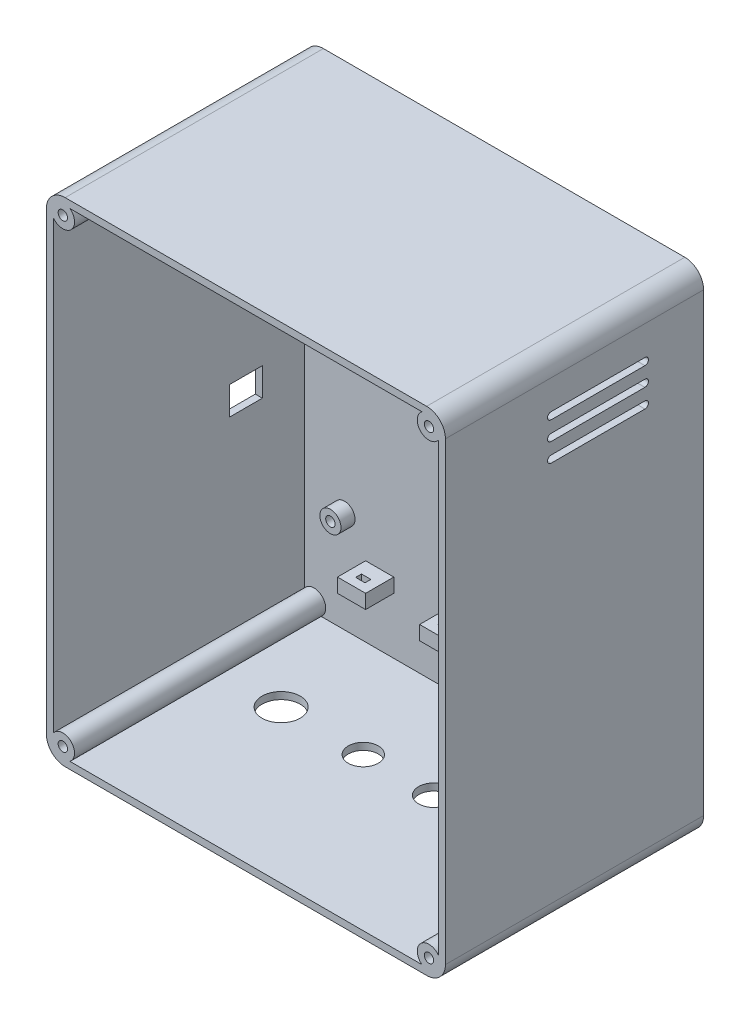
SolidWorks part; units mm, degrees
ref_plane "Front Plane" through (0, 0, 0) normal (0, 0, 1) x (1, 0, 0)
ref_plane "Top Plane" through (0, 0, 0) normal (0, 1, 0) x (1, 0, 0)
ref_plane "Right Plane" through (0, 0, 0) normal (1, 0, 0) x (0, 0, -1)
sketch "Sketch1" plane through (0, 0, 0) normal (0, 0, 1) x (1, 0, 0)
  line L0 (-77, 0) -> (77, 0)
  line L1 (85, 8) -> (85, 202)
  line L2 (77, 210) -> (-77, 210)
  line L3 (-85, 202) -> (-85, 8)
  arc A0 (-85, 8) -> (-77, 0) centre (-77, 8) ccw
  arc A1 (77, 0) -> (85, 8) centre (77, 8) ccw
  arc A2 (85, 202) -> (77, 210) centre (77, 202) ccw
  arc A3 (-77, 210) -> (-85, 202) centre (-77, 202) ccw
extrude "Block" add sketch "Sketch1" along normal blind 110
shell "Shell1" thickness 3 removed face at (0, 105, 110)
sketch "Sketch2" plane through (0, 0, 0) normal (0, 0, 1) x (1, 0, 0)
  circle A0 centre (-78, 7) radius 5
  circle A1 centre (78, 7) radius 5
  circle A2 centre (-78, 203) radius 5
  circle A3 centre (78, 203) radius 5
extrude "Corner columns" add sketch "Sketch2" along normal blind 110
ref_plane "P1_Front_110" through (0, 0, 110) normal (0, 0, 1) x (1, 0, 0)
sketch "Sketch3" plane through (0, 0, 110) normal (0, 0, 1) x (1, 0, 0)
  circle A0 centre (-78, 7) radius 2
  circle A1 centre (78, 7) radius 2
  circle A2 centre (-78, 203) radius 2
  circle A3 centre (78, 203) radius 2
extrude "Front panel insert holes" cut sketch "Sketch3" against normal blind 7
ref_plane "P2_Front_3" through (0, 0, 3) normal (0, 0, 1) x (1, 0, 0)
sketch "Sketch4" plane through (0, 0, 3) normal (0, 0, 1) x (1, 0, 0)
  circle A0 centre (-65, 46) radius 4.5
  circle A1 centre (65, 46) radius 4.5
  circle A2 centre (-65, 190) radius 4.5
  circle A3 centre (65, 190) radius 4.5
extrude "Plate bosses" add sketch "Sketch4" along normal blind 6
ref_plane "P3_Front_9" through (0, 0, 9) normal (0, 0, 1) x (1, 0, 0)
sketch "Sketch5" plane through (0, 0, 9) normal (0, 0, 1) x (1, 0, 0)
  circle A0 centre (-65, 46) radius 2
  circle A1 centre (65, 46) radius 2
  circle A2 centre (-65, 190) radius 2
  circle A3 centre (65, 190) radius 2
extrude "Plate insert holes" cut sketch "Sketch5" against normal blind 7
sketch "Sketch6" plane through (0, 0, 0) normal (0, 1, 0) x (1, 0, 0)
  circle A0 centre (-50, -45) radius 8.15
  circle A1 centre (-15, -45) radius 6.4
  circle A2 centre (15, -45) radius 6.4
  circle A3 centre (50, -45) radius 6.4
extrude "Cable gland holes" cut sketch "Sketch6" along normal blind 4
sketch "Sketch7" plane through (0, 0, 3) normal (0, 0, 1) x (1, 0, 0)
  line L1 (-56, 27) -> (-44, 27)
  line L2 (-56, 27) -> (-56, 33)
  line L3 (-56, 33) -> (-44, 33)
  line L4 (-44, 27) -> (-44, 33)
  line L5 (-56, 27) -> (-44, 33) construction
  line L6 (-56, 33) -> (-44, 27) construction
  line L7 (-21, 27) -> (-9, 27)
  line L8 (-21, 27) -> (-21, 33)
  line L9 (-21, 33) -> (-9, 33)
  line L10 (-9, 27) -> (-9, 33)
  line L11 (-21, 27) -> (-9, 33) construction
  line L12 (-21, 33) -> (-9, 27) construction
  line L13 (9, 27) -> (21, 27)
  line L14 (9, 27) -> (9, 33)
  line L15 (9, 33) -> (21, 33)
  line L16 (21, 27) -> (21, 33)
  line L17 (9, 27) -> (21, 33) construction
  line L18 (9, 33) -> (21, 27) construction
  line L19 (44, 27) -> (56, 27)
  line L20 (44, 27) -> (44, 33)
  line L21 (44, 33) -> (56, 33)
  line L22 (56, 27) -> (56, 33)
  line L23 (44, 27) -> (56, 33) construction
  line L24 (44, 33) -> (56, 27) construction
  point P0 (-50, 30)
  point P5 (-15, 30)
  point P10 (15, 30)
  point P15 (50, 30)
extrude "Cable tie bars" add sketch "Sketch7" along normal blind 12
ref_plane "P4_Top_26.99" through (0, 26.99, 0) normal (0, 1, 0) x (1, 0, 0)
sketch "Sketch8" plane through (0, 26.99, 0) normal (0, 1, 0) x (1, 0, 0)
  line L1 (-52, -11.25) -> (-48, -11.25)
  line L2 (-52, -11.25) -> (-52, -8.75)
  line L3 (-52, -8.75) -> (-48, -8.75)
  line L4 (-48, -11.25) -> (-48, -8.75)
  line L5 (-52, -11.25) -> (-48, -8.75) construction
  line L6 (-52, -8.75) -> (-48, -11.25) construction
  line L7 (-17, -11.25) -> (-13, -11.25)
  line L8 (-17, -11.25) -> (-17, -8.75)
  line L9 (-17, -8.75) -> (-13, -8.75)
  line L10 (-13, -11.25) -> (-13, -8.75)
  line L11 (-17, -11.25) -> (-13, -8.75) construction
  line L12 (-17, -8.75) -> (-13, -11.25) construction
  line L13 (13, -11.25) -> (17, -11.25)
  line L14 (13, -11.25) -> (13, -8.75)
  line L15 (13, -8.75) -> (17, -8.75)
  line L16 (17, -11.25) -> (17, -8.75)
  line L17 (13, -11.25) -> (17, -8.75) construction
  line L18 (13, -8.75) -> (17, -11.25) construction
  line L19 (48, -11.25) -> (52, -11.25)
  line L20 (48, -11.25) -> (48, -8.75)
  line L21 (48, -8.75) -> (52, -8.75)
  line L22 (52, -11.25) -> (52, -8.75)
  line L23 (48, -11.25) -> (52, -8.75) construction
  line L24 (48, -8.75) -> (52, -11.25) construction
  point P0 (-50, -10)
  point P5 (-15, -10)
  point P10 (15, -10)
  point P15 (50, -10)
extrude "Cable tie slots" cut sketch "Sketch8" along normal blind 6.02
ref_plane "P5_Right_-85" through (-85, 0, 0) normal (1, 0, 0) x (0, 0, -1)
sketch "Sketch9" plane through (-85, 0, 0) normal (1, 0, 0) x (0, 0, -1)
  line L1 (-35, 89) -> (-21, 89)
  line L2 (-35, 89) -> (-35, 101)
  line L3 (-35, 101) -> (-21, 101)
  line L4 (-21, 89) -> (-21, 101)
  line L5 (-35, 89) -> (-21, 101) construction
  line L6 (-35, 101) -> (-21, 89) construction
  point P0 (-28, 95)
extrude "USB access" cut sketch "Sketch9" along normal blind 4
ref_plane "P6_Right_-85" through (-85, 0, 0) normal (1, 0, 0) x (0, 0, -1)
sketch "Sketch10" plane through (-85, 0, 0) normal (1, 0, 0) x (0, 0, -1)
  line L0 (-25, 172) -> (-65, 172) construction
  line L1 (-25, 170.5) -> (-65, 170.5)
  line L2 (-25, 173.5) -> (-65, 173.5)
  line L3 (-25, 180) -> (-65, 180) construction
  line L4 (-25, 178.5) -> (-65, 178.5)
  line L5 (-25, 181.5) -> (-65, 181.5)
  line L6 (-25, 188) -> (-65, 188) construction
  line L7 (-25, 186.5) -> (-65, 186.5)
  line L8 (-25, 189.5) -> (-65, 189.5)
  arc A0 (-25, 170.5) -> (-25, 173.5) centre (-25, 172) ccw
  arc A1 (-65, 173.5) -> (-65, 170.5) centre (-65, 172) ccw
  arc A2 (-25, 178.5) -> (-25, 181.5) centre (-25, 180) ccw
  arc A3 (-65, 181.5) -> (-65, 178.5) centre (-65, 180) ccw
  arc A4 (-25, 186.5) -> (-25, 189.5) centre (-25, 188) ccw
  arc A5 (-65, 189.5) -> (-65, 186.5) centre (-65, 188) ccw
  point P2 (-45, 172)
  point P7 (-45, 180)
  point P14 (-45, 188)
extrude "Vents left" cut sketch "Sketch10" along normal blind 4
ref_plane "P7_Right_85" through (85, 0, 0) normal (1, 0, 0) x (0, 0, -1)
sketch "Sketch11" plane through (85, 0, 0) normal (1, 0, 0) x (0, 0, -1)
  line L0 (-25, 172) -> (-65, 172) construction
  line L1 (-25, 170.5) -> (-65, 170.5)
  line L2 (-25, 173.5) -> (-65, 173.5)
  line L3 (-25, 180) -> (-65, 180) construction
  line L4 (-25, 178.5) -> (-65, 178.5)
  line L5 (-25, 181.5) -> (-65, 181.5)
  line L6 (-25, 188) -> (-65, 188) construction
  line L7 (-25, 186.5) -> (-65, 186.5)
  line L8 (-25, 189.5) -> (-65, 189.5)
  arc A0 (-25, 170.5) -> (-25, 173.5) centre (-25, 172) ccw
  arc A1 (-65, 173.5) -> (-65, 170.5) centre (-65, 172) ccw
  arc A2 (-25, 178.5) -> (-25, 181.5) centre (-25, 180) ccw
  arc A3 (-65, 181.5) -> (-65, 178.5) centre (-65, 180) ccw
  arc A4 (-25, 186.5) -> (-25, 189.5) centre (-25, 188) ccw
  arc A5 (-65, 189.5) -> (-65, 186.5) centre (-65, 188) ccw
  point P2 (-45, 172)
  point P7 (-45, 180)
  point P14 (-45, 188)
extrude "Vents right" cut sketch "Sketch11" against normal blind 4
sketch "Sketch12" plane through (0, 0, 0) normal (0, 0, 1) x (1, 0, 0)
  circle A0 centre (-45, 165) radius 4.75
  circle A1 centre (45, 165) radius 4.75
extrude "Keyhole heads" cut sketch "Sketch12" along normal blind 4
sketch "Sketch13" plane through (0, 0, 0) normal (0, 0, 1) x (1, 0, 0)
  line L0 (-45, 165) -> (-45, 176) construction
  line L1 (-47.15, 165) -> (-47.15, 176)
  line L2 (-42.85, 165) -> (-42.85, 176)
  line L3 (45, 165) -> (45, 176) construction
  line L4 (42.85, 165) -> (42.85, 176)
  line L5 (47.15, 165) -> (47.15, 176)
  arc A0 (-47.15, 165) -> (-42.85, 165) centre (-45, 165) ccw
  arc A1 (-42.85, 176) -> (-47.15, 176) centre (-45, 176) ccw
  arc A2 (42.85, 165) -> (47.15, 165) centre (45, 165) ccw
  arc A3 (47.15, 176) -> (42.85, 176) centre (45, 176) ccw
  point P2 (-45, 170.5)
  point P7 (45, 170.5)
extrude "Keyhole slots" cut sketch "Sketch13" along normal blind 4
